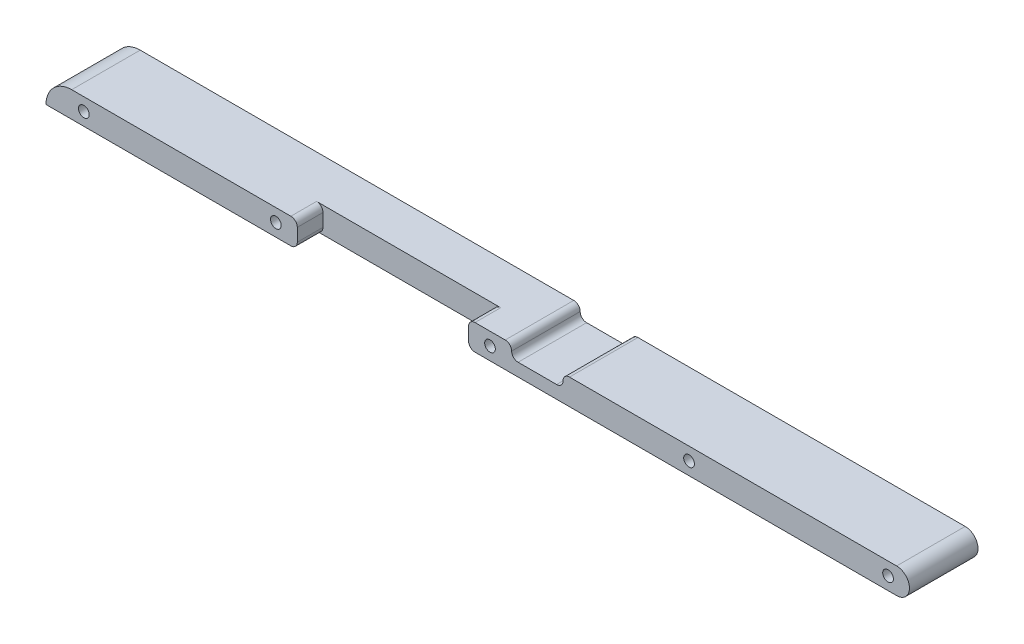
SolidWorks part; units mm, degrees
material "POM Ацеталь кополимер"
ref_plane "Спереди" through (0, 0, 0) normal (0, 0, 1) x (1, 0, 0)
ref_plane "Сверху" through (0, 0, 0) normal (0, 1, 0) x (1, 0, 0)
ref_plane "Справа" through (0, 0, 0) normal (1, 0, 0) x (0, 0, -1)
sketch "Model" plane through (0, 0, 0) normal (0, 0, 1) x (1, 0, 0)
  line L0 (100.82, 3) -> (0, 3)
  line L1 (0, 0) -> (100.82, 0)
  line L21 (100.82, 3) -> (100.82, 0)
  line L22 (0, 3) -> (0, 0)
  dimension "D2" = 100.82
  dimension "D3" = 3
extrude "База" add sketch "Model" along normal blind 8
sketch "Эскиз2" plane through (0, 0, 8) normal (0, 0, 1) x (1, 0, 0)
  line L0 (100.82, 3) -> (0, 3) construction
  line L1 (29.34, 3) -> (49.34, 3)
  line L2 (29.34, 3) -> (29.34, 0)
  line L3 (29.34, 0) -> (49.34, 0)
  line L4 (49.34, 3) -> (49.34, 0)
  line L5 (0, 0) -> (100.82, 0) construction
  dimension "D1" = 20
  dimension "D2" = 29.34
extrude "Вырез шестерни" cut sketch "Эскиз2" against normal blind 3
hole_wizard "Резьба М1.6" positions "Эскиз3" profile "Эскиз4" tap size "M1.6" standard "DIN" end condition through all
sketch "Эскиз3" plane through (0, 0, 8) normal (0, 0, 1) x (1, 0, 0)
  line L0 (4.42, 1.5) -> (4.42, 3) construction
  line L1 (29.34, 3) -> (0, 3) construction
  line L4 (4.42, 1.5) -> (4.42, 0) construction
  line L5 (0, 0) -> (29.34, 0) construction
  line L10 (51.84, 1.5) -> (49.34, 1.5) construction
  line L11 (49.34, 0) -> (49.34, 3) construction
  line L18 (98.32, 1.5) -> (100.82, 1.5) construction
  line L19 (100.82, 0) -> (100.82, 3) construction
  line L20 (29.34, 3) -> (29.34, 0) construction
  line L21 (51.84, 1.5) -> (75.08, 1.5) construction
  line L22 (75.08, 1.5) -> (98.32, 1.5) construction
  point P0 (4.42, 1.5)
  point P19 (51.84, 1.5)
  point P25 (75.08, 1.5)
  point P44 (98.32, 1.5)
  point P57 (100.82, 1.5)
  point P63 (26.84, 1.5)
  dimension "D2" = 4.42
  dimension "D3" = 2.5
  dimension "D4" = 2.5
  dimension "D5" = 2.5
sketch "Эскиз4" plane through (4.42, 1.5, 8) normal (1, 0, 0) x (0, -1, 0)
  line L0 (0, 0) -> (0, 8)
  line L1 (0, 8) -> (0.625, 8)
  line L2 (0.625, 8) -> (0.625, 0)
  line L5 (0.625, 0) -> (0, 0)
  line L11 (0, -6.35) -> (0, 107.95) construction
  dimension "Диаметр проходного сверла" = 1.25
  dimension "Глубина проходного сверла" = 8
cosmetic thread "Отверстие резьбы1" parameters "D2"=1.6
cosmetic thread "Отверстие резьбы2" parameters "D2"=1.6
cosmetic thread "Отверстие резьбы3" parameters "D2"=1.6
cosmetic thread "Отверстие резьбы4" parameters "D2"=1.6
cosmetic thread "Отверстие резьбы5" parameters "D2"=1.6
sketch "Эскиз7" plane through (0, 0, 8) normal (0, 0, 1) x (1, 0, 0)
  line L0 (100.82, 3) -> (49.34, 3) construction
  line L1 (54.37, 3) -> (60.37, 3)
  line L2 (54.37, 3) -> (54.37, 1.5)
  line L3 (54.37, 1.5) -> (60.37, 1.5)
  line L4 (60.37, 3) -> (60.37, 1.5)
  line L10 (57.37, 1.5) -> (57.37, 3) construction
  line L11 (57.37, 1.5) -> (57.37, 0) construction
  line L12 (49.34, 0) -> (100.82, 0) construction
  dimension "D1" = 57.37
  dimension "D3" = 6
extrude "Вырез крепления двигателя" cut sketch "Эскиз7" against normal through all
fillet "Скругление1" 2 edges at (100.82, 3, 4) (100.82, 0, 4) type full round first side face at (80.595, 3, 4) second side face at (44.875, 0, 5.25) middle face at (100.82, 1.5, 4)
fillet "Скругление2" radius 3 1 edges at (0, 3, 4)
fillet "Скругление4" radius 0.75 8 edges at (60.37, 1.5, 4) (60.37, 3, 4) (54.37, 1.5, 4) (54.37, 3, 4) (49.34, 3, 6.5) (29.34, 3, 6.5) (49.34, 0, 6.5) (29.34, 0, 6.5)
